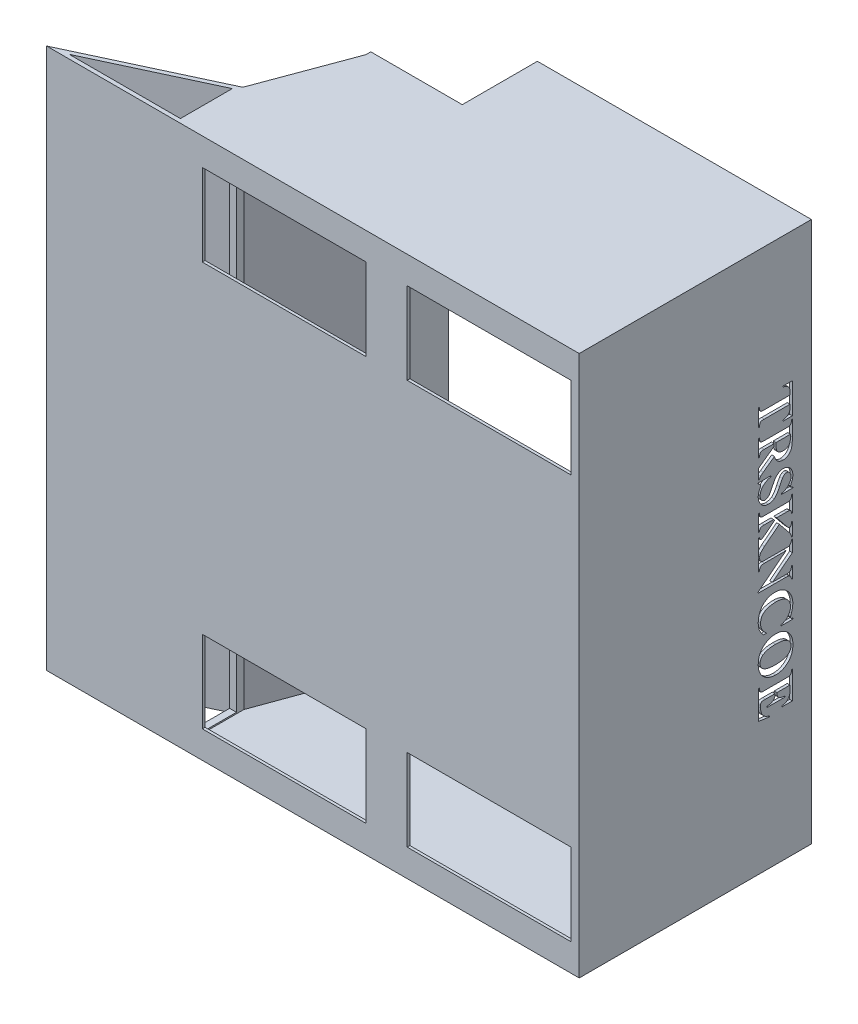
SolidWorks part; units mm, degrees
material "Plain Carbon Steel"
ref_plane "Front Plane" through (0, 0, 0) normal (0, 0, 1) x (1, 0, 0)
ref_plane "Top Plane" through (0, 0, 0) normal (0, 1, 0) x (1, 0, 0)
ref_plane "Right Plane" through (0, 0, 0) normal (1, 0, 0) x (0, 0, -1)
sketch "Sketch1" plane through (0, 0, 0) normal (0, 1, 0) x (1, 0, 0)
  line L0 (-61.935, -72.4964) -> (-16.4457, -51.2844)
  line L3 (127.5543, 35.5036) -> (127.5543, -72.4964)
  line L4 (127.5543, -72.4964) -> (-61.935, -72.4964)
  line L6 (128.5543, 36.5036) -> (128.5543, -73.4964)
  line L7 (128.5543, -73.4964) -> (-66.4457, -73.4964)
  line L8 (-66.4457, -73.4964) -> (-17.4457, -50.6473)
  line L10 (-16.4457, 35.5036) -> (127.5543, 35.5036) construction
  line L11 (-17.4457, 36.5036) -> (128.5543, 36.5036) construction
  line L13 (127.5543, 35.5036) -> (128.5543, 36.5036)
  line L14 (-16.4457, -51.2844) -> (-16.4457, 35.5036) construction
  line L15 (-17.4457, -50.6473) -> (-17.4457, 36.5036) construction
  line L16 (-16.4457, -51.2844) -> (-4.2595, -17.8031)
  line L17 (-4.2595, -17.8031) -> (-4.2595, 36.5036)
  line L18 (-4.2595, 36.5036) -> (-5.2595, 36.5036)
  line L21 (-5.2595, 36.5036) -> (-5.2595, -17.8031)
  line L22 (-5.2595, -17.8031) -> (-17.4457, -50.6473)
  dimension "D1" = 195
  dimension "D2" = 25
  dimension "D3" = 1
  dimension "D4" = 110
  dimension "D5" = 50
  dimension "D6" = 135
  dimension "D7" = 110
  dimension "D8" = 1
extrude "Boss-Extrude2" add sketch "Sketch1" along normal blind 198
sketch "Sketch3" plane through (0, 0, 73.4964) normal (0, 0, 1) x (1, 0, 0)
sketch "Sketch5" plane through (0, 0, 72.4964) normal (0, 0, -1) x (-1, 0, 0)
  line L0 (-127.5543, 198) -> (61.935, 198) construction
  line L1 (-125.5543, 188) -> (-65.5543, 188)
  line L2 (-125.5543, 188) -> (-125.5543, 158)
  line L3 (-125.5543, 158) -> (-65.5543, 158)
  line L4 (-65.5543, 188) -> (-65.5543, 158)
  line L5 (-125.5543, 188) -> (-65.5543, 158) construction
  line L6 (-125.5543, 158) -> (-65.5543, 188) construction
  line L7 (-50.5543, 188) -> (9.4457, 188)
  line L8 (-50.5543, 188) -> (-50.5543, 158)
  line L9 (-50.5543, 158) -> (9.4457, 158)
  line L10 (9.4457, 188) -> (9.4457, 158)
  line L11 (-50.5543, 188) -> (9.4457, 158) construction
  line L12 (-50.5543, 158) -> (9.4457, 188) construction
  line L13 (-125.5543, 40) -> (-65.5543, 40)
  line L14 (-125.5543, 40) -> (-125.5543, 10)
  line L15 (-125.5543, 10) -> (-65.5543, 10)
  line L16 (-65.5543, 40) -> (-65.5543, 10)
  line L17 (-125.5543, 40) -> (-65.5543, 10) construction
  line L18 (-125.5543, 10) -> (-65.5543, 40) construction
  line L19 (-50.5543, 40) -> (9.4457, 40)
  line L20 (-50.5543, 40) -> (-50.5543, 10)
  line L21 (-50.5543, 10) -> (9.4457, 10)
  line L22 (9.4457, 40) -> (9.4457, 10)
  line L23 (-50.5543, 40) -> (9.4457, 10) construction
  line L24 (-50.5543, 10) -> (9.4457, 40) construction
  line L25 (-127.5543, 0) -> (61.935, 0) construction
  line L27 (-128.5543, 198) -> (-128.5543, 0) construction
  point P0 (-95.5543, 173)
  point P5 (-20.5543, 173)
  point P10 (-95.5543, 25)
  point P15 (-20.5543, 25)
  dimension "D1" = 60
  dimension "D2" = 60
  dimension "D3" = 60
  dimension "D4" = 60
  dimension "D5" = 15
  dimension "D6" = 15
  dimension "D7" = 25
  dimension "D8" = 25
  dimension "D9" = 33
  dimension "D10" = 33
  dimension "D11" = 30
  dimension "D12" = 30
  dimension "D13" = 30
  dimension "D14" = 30
  dimension "D15" = 25
  dimension "D16" = 25
extrude "Cut-Extrude5" cut sketch "Sketch5" against normal blind 33
sketch "Sketch8" plane through (0, 0, 0) normal (0, -1, 0) x (-1, 0, 0)
  line L0 (16.4457, -51.2844) -> (16.4457, -72.4964)
  line L1 (-127.5543, -72.4964) -> (61.935, -72.4964) construction
  line L2 (16.4457, -72.4964) -> (61.935, -72.4964)
  line L3 (61.935, -72.4964) -> (16.4457, -51.2844)
extrude "Boss-Extrude5" add sketch "Sketch8" against normal blind 198
sketch "Sketch10" plane through (0, 198, 0) normal (0, 1, 0) x (1, 0, 0)
  line L0 (127.5543, -72.4964) -> (127.5543, 35.5036)
  line L2 (-4.2595, 36.5036) -> (-4.2595, -17.8031)
  line L3 (-4.2595, -17.8031) -> (-16.4457, -51.2844)
  line L4 (-16.4457, -51.2844) -> (-16.4457, -72.4964)
  line L5 (-16.4457, -72.4964) -> (127.5543, -72.4964)
  line L6 (-4.2595, 36.5036) -> (128.5543, 36.5036)
  line L7 (128.5543, 36.5036) -> (127.5543, 35.5036)
extrude "Boss-Extrude6" add sketch "Sketch10" against normal blind 1.5
sketch "Sketch11" plane through (0, 0, 0) normal (0, -1, 0) x (-1, 0, 0)
  line L0 (4.2595, 36.5036) -> (4.2595, -17.8031)
  line L1 (4.2595, -17.8031) -> (16.4457, -51.2844)
  line L2 (16.4457, -51.2844) -> (16.4457, -72.4964)
  line L3 (16.4457, -72.4964) -> (-127.5543, -72.4964)
  line L4 (-127.5543, -72.4964) -> (-127.5543, 35.5036)
  line L5 (-127.5543, 35.5036) -> (-128.5543, 36.5036)
  line L6 (-128.5543, 36.5036) -> (4.2595, 36.5036)
extrude "Boss-Extrude7" add sketch "Sketch11" against normal blind 1.5
sketch "Sketch12" plane through (-5.2595, 0, 0) normal (-1, 0, 0) x (0, 0, 1)
  line L5 (-36.5036, 198) -> (-36.5036, 0) construction
  line L6 (6.4964, 84) -> (16.4964, 84)
  line L16 (6.4964, 84) -> (6.4964, 114)
  line L17 (6.4964, 114) -> (16.4964, 114)
  line L18 (16.4964, 84) -> (16.4964, 114)
  line L19 (6.4964, 84) -> (16.4964, 114) construction
  line L20 (6.4964, 114) -> (16.4964, 84) construction
  point P0 (11.4964, 99)
  dimension "D1" = 30
  dimension "D4" = 10
  dimension "D5" = 99
  dimension "4" = 48
extrude "Cut-Extrude8" cut sketch "Sketch12" against normal blind 2.5
sketch "Sketch13" plane through (0, 198, 0) normal (0, 1, 0) x (1, 0, 0)
  line L0 (128.5543, -73.4964) -> (128.5543, 36.5036) construction
  line L1 (-5.2595, 36.5036) -> (128.5543, 36.5036)
  line L2 (-5.2595, 36.5036) -> (-5.2595, 11.5036)
  line L3 (-5.2595, 11.5036) -> (128.5543, 11.5036)
  line L4 (128.5543, 36.5036) -> (128.5543, 11.5036)
  dimension "D1" = 25
extrude "Cut-Extrude9" cut sketch "Sketch13" against normal blind 200
sketch "Sketch19" plane through (0, 0, 0) normal (0, -1, 0) x (-1, 0, 0)
  line L0 (66.4457, -73.4964) -> (17.4457, -50.6473)
  line L1 (17.4457, -50.6473) -> (17.4457, -73.4964)
  line L2 (66.4457, -73.4964) -> (-128.5543, -73.4964) construction
  line L3 (66.4457, -73.4964) -> (17.4457, -73.4964)
  line L4 (59.6796, -71.9964) -> (18.9457, -71.9964)
  line L5 (18.9457, -53.0018) -> (18.9457, -71.9964)
  line L6 (59.6796, -71.9964) -> (18.9457, -53.0018)
  dimension "D1" = 1.5
sketch "Sketch20" plane through (-16.4457, 0, 0) normal (1, 0, 0) x (0, 0, -1)
  line L5 (-73.4964, 198) -> (11.5036, 198) construction
  line L6 (-71.9964, 196) -> (-53.9964, 196)
  line L7 (-71.9964, 196) -> (-71.9964, 2)
  line L8 (-71.9964, 2) -> (-53.9964, 2)
  line L9 (-53.9964, 196) -> (-53.9964, 2)
  line L10 (-73.4964, 198) -> (-73.4964, 0) construction
  line L11 (-73.4964, 0) -> (11.5036, 0) construction
  dimension "D1" = 2
  dimension "D2" = 1.5
  dimension "D3" = 2
  dimension "D4" = 18
extrude "Cut-Extrude13" cut sketch "Sketch19" against normal blind 301 contours L4 L5 L6
extrude "Cut-Extrude14" cut sketch "Sketch20" against normal blind 3
sketch "Sketch21" plane through (128.5543, 0, 0) normal (1, 0, 0) x (0, 0, -1)
  line L0 (-7.7952, 198) -> (-7.7952, 0) construction
  line L1 (-73.4964, 198) -> (11.5036, 198) construction
  line L2 (-73.4964, 0) -> (11.5036, 0) construction
sketch "Sketch22" plane through (128.5543, 0, 0) normal (1, 0, 0) x (0, 0, -1)
  text T0 "TRSKNCOE" font "Times New Roman" height in points 48
extrude "Cut-Extrude16" cut sketch "Sketch22" against normal blind 10
sketch "Sketch23" plane through (0, 0, -11.5036) normal (0, 0, -1) x (-1, 0, 0)
  line L0 (-29.7405, 0) -> (5.2595, 35)
  line L1 (-128.5543, 0) -> (5.2595, 0) construction
  line L2 (5.2595, 198) -> (5.2595, 0) construction
  line L3 (5.2595, 35) -> (5.2595, 0)
  line L4 (5.2595, 0) -> (-29.7405, 0)
  line L5 (-128.5543, 99) -> (5.2595, 99) construction
  line L6 (-128.5543, 198) -> (-128.5543, 0) construction
  line L7 (5.2595, 198) -> (-29.7405, 198)
  line L8 (5.2595, 163) -> (5.2595, 198)
  line L9 (-29.7405, 198) -> (5.2595, 163)
  dimension "D1" = 49.4975
extrude "Cut-Extrude17" cut sketch "Sketch23" against normal blind 29
sketch "Sketch24" plane through (0, 0, -11.5036) normal (0, 0, -1) x (-1, 0, 0)
  line L0 (-29.7405, 0) -> (5.2595, 35)
  line L1 (5.2595, 198) -> (5.2595, 0) construction
  line L2 (5.2595, 35) -> (4.2595, 34) construction
  line L3 (5.2595, 35) -> (5.2595, 33.5)
  line L4 (5.2595, 33.5) -> (-28.2405, 0)
  line L5 (-29.7405, 0) -> (5.2595, 0) construction
  line L6 (-28.2405, 0) -> (-29.7405, 0)
  line L7 (-128.5543, 99) -> (5.2595, 99) construction
  line L8 (-128.5543, 198) -> (-128.5543, 0) construction
  line L9 (-28.2405, 198) -> (-29.7405, 198)
  line L10 (5.2595, 164.5) -> (-28.2405, 198)
  line L11 (5.2595, 163) -> (5.2595, 164.5)
  line L12 (-29.7405, 198) -> (5.2595, 163)
  dimension "D1" = 1.5
extrude "Boss-Extrude8" add sketch "Sketch24" against normal blind 29
sketch "Sketch26" plane through (0, 0, 17.4964) normal (0, 0, -1) x (-1, 0, 0)
  line L0 (-28.2405, 0) -> (5.2595, 33.5)
  line L1 (5.2595, 33.5) -> (5.2595, 0)
  line L2 (5.2595, 0) -> (-28.2405, 0)
  line L3 (-28.2405, 198) -> (5.2595, 198)
  line L4 (5.2595, 198) -> (5.2595, 164.5)
  line L5 (5.2595, 164.5) -> (-28.2405, 198)
extrude "Boss-Extrude10" add sketch "Sketch26" along normal blind 1.5
sketch "Sketch27" plane through (14.1203, 14.1203, 0) normal (-0.7071, -0.7071, 0) x (0, 0, 1)
  line L0 (-11.5036, -19.9691) -> (-11.5036, 27.4071) construction
  line L5 (4.4964, -11.281) -> (14.4964, -11.281)
  line L6 (4.4964, -11.281) -> (4.4964, 18.719)
  line L7 (4.4964, 18.719) -> (14.4964, 18.719)
  line L8 (14.4964, -11.281) -> (14.4964, 18.719)
  line L9 (4.4964, -11.281) -> (14.4964, 18.719) construction
  line L10 (4.4964, 18.719) -> (14.4964, -11.281) construction
  point P0 (9.4964, 3.719)
  point P7 (-11.5036, 3.719)
  dimension "D1" = 30
  dimension "D2" = 10
  dimension "D3" = 21
  dimension "D4" = 0
extrude "Cut-Extrude18" cut sketch "Sketch27" against normal blind 1.5
sketch "Sketch29" plane through (-84.8797, 84.8797, 0) normal (-0.7071, 0.7071, 0) x (0, 0, 1)
  line L0 (-11.5036, 112.6001) -> (-11.5036, 159.9762) construction
  line L1 (4.4964, 121.2881) -> (14.4964, 121.2881)
  line L2 (4.4964, 121.2881) -> (4.4964, 151.2881)
  line L3 (4.4964, 151.2881) -> (14.4964, 151.2881)
  line L4 (14.4964, 121.2881) -> (14.4964, 151.2881)
  line L5 (4.4964, 121.2881) -> (14.4964, 151.2881) construction
  line L6 (4.4964, 151.2881) -> (14.4964, 121.2881) construction
  point P0 (9.4964, 136.2881)
  point P7 (-11.5036, 136.2881)
  dimension "D1" = 30
  dimension "D2" = 10
  dimension "D3" = 0
  dimension "D4" = 21
extrude "Cut-Extrude19" cut sketch "Sketch29" against normal blind 1.5
